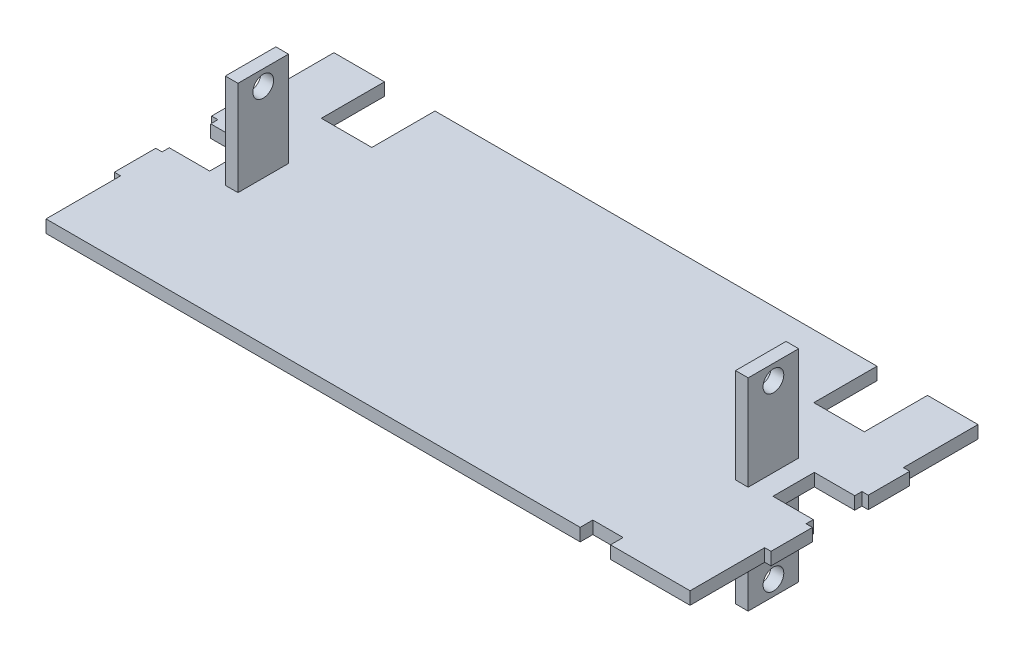
SolidWorks part; units mm, degrees
ref_plane "Front Plane" through (0, 0, 0) normal (0, 0, 1) x (1, 0, 0)
ref_plane "Top Plane" through (0, 0, 0) normal (0, 1, 0) x (1, 0, 0)
ref_plane "Right Plane" through (0, 0, 0) normal (1, 0, 0) x (0, 0, -1)
sketch "Sketch1" plane through (0, 0, 0) normal (0, 1, 0) x (1, 0, 0)
  line L0 (0, 72.39) -> (0, -72.39) construction
  line L1 (161.925, -72.39) -> (121.92, -72.39)
  line L2 (161.925, -72.39) -> (161.925, -34.8747)
  line L3 (161.925, 72.39) -> (136.525, 72.39)
  line L4 (-161.925, -72.39) -> (-161.925, -34.8747)
  line L5 (161.925, -72.39) -> (-161.925, 72.39) construction
  line L6 (161.925, 72.39) -> (-161.925, -72.39) construction
  line L7 (161.925, 10.414) -> (141.605, 10.414)
  line L9 (161.925, -10.414) -> (141.605, -10.414)
  line L10 (141.605, 10.414) -> (141.605, -10.414)
  line L11 (-136.525, 72.39) -> (-161.925, 72.39)
  line L13 (-161.925, -10.414) -> (-141.605, -10.414)
  line L14 (-141.605, 10.414) -> (-141.605, -10.414)
  line L15 (-161.925, 10.414) -> (-141.605, 10.414)
  line L17 (-127, 0) -> (127, 0) construction
  line L18 (-161.925, 14.0467) -> (-165.1, 14.0467)
  line L20 (-161.925, 34.8747) -> (-165.1, 34.8747)
  line L21 (-165.1, 14.0467) -> (-165.1, 34.8747)
  line L22 (-161.925, -34.8747) -> (-165.1, -34.8747)
  line L23 (-165.1, -14.0467) -> (-165.1, -34.8747)
  line L24 (-161.925, -14.0467) -> (-165.1, -14.0467)
  line L27 (161.925, -14.0467) -> (165.1, -14.0467)
  line L28 (165.1, -14.0467) -> (165.1, -34.8747)
  line L29 (161.925, -34.8747) -> (165.1, -34.8747)
  line L30 (161.925, 34.8747) -> (165.1, 34.8747)
  line L31 (165.1, 14.0467) -> (165.1, 34.8747)
  line L32 (161.925, 14.0467) -> (165.1, 14.0467)
  line L34 (-161.925, 34.8747) -> (-161.925, 72.39)
  line L35 (-161.925, -14.0467) -> (-161.925, -10.414)
  line L36 (161.925, 34.8747) -> (161.925, 72.39)
  line L37 (161.925, -14.0467) -> (161.925, -10.414)
  line L38 (-161.925, 10.414) -> (-161.925, 14.0467)
  line L39 (161.925, 10.414) -> (161.925, 14.0467)
  line L40 (-136.525, 72.39) -> (-136.525, 40.64)
  line L41 (-136.525, 40.64) -> (-111.125, 40.64)
  line L42 (-111.125, 72.39) -> (-111.125, 40.64)
  line L44 (111.125, 72.39) -> (111.125, 40.64)
  line L45 (111.125, 40.64) -> (136.525, 40.64)
  line L46 (136.525, 72.39) -> (136.525, 40.64)
  line L47 (111.125, 72.39) -> (-111.125, 72.39)
  line L48 (106.68, -72.39) -> (-161.925, -72.39)
  line L50 (106.68, -72.39) -> (106.68, -66.04)
  line L51 (106.68, -66.04) -> (121.92, -66.04)
  line L52 (121.92, -72.39) -> (121.92, -66.04)
  point P0 (0, 0)
  point P6 (127, 0)
  point P47 (121.92, -69.215)
  dimension "D1" = 323.85
  dimension "D2" = 144.78
  dimension "D3" = 20.828
  dimension "D5" = 3.175
  dimension "D6" = 20.828
  dimension "D4" = 20.32
  dimension "D7" = 31.75
  dimension "D8" = 25.4
  dimension "D9" = 25.4
  dimension "D10" = 31.75
  dimension "D12" = 25.4
  dimension "D11" = 25.4
  dimension "D13" = 15.24
  dimension "D14" = 6.35
  dimension "D15" = 40.005
extrude "Boss-Extrude1" add sketch "Sketch1" along normal mid plane 6.35
sketch "Sketch2" plane through (0, 0, 0) normal (0, 1, 0) x (1, 0, 0)
  line L0 (-141.605, 10.414) -> (-141.605, -10.414) construction
  line L1 (125.095, -12.7) -> (131.445, -12.7)
  line L2 (125.095, -12.7) -> (125.095, 12.7)
  line L3 (125.095, 12.7) -> (131.445, 12.7)
  line L4 (131.445, -12.7) -> (131.445, 12.7)
  line L5 (125.095, -12.7) -> (131.445, 12.7) construction
  line L6 (125.095, 12.7) -> (131.445, -12.7) construction
  line L9 (-125.095, -12.7) -> (-125.095, 12.7)
  line L10 (-125.095, 12.7) -> (-131.445, 12.7)
  line L11 (-131.445, -12.7) -> (-131.445, 12.7)
  line L12 (-125.095, -12.7) -> (-131.445, -12.7)
  line L13 (141.605, -10.414) -> (141.605, 10.414) construction
  point P0 (128.27, 0)
  point P10 (141.605, 0)
  dimension "D1" = 10.16
  dimension "D2" = 10.16
  dimension "D3" = 25.4
  dimension "D4" = 25.4
  dimension "D5" = 6.35
  dimension "D6" = 6.35
  dimension "D7" = 6.35
extrude "Boss-Extrude2" add sketch "Sketch2" along normal mid plane 101.6
sketch "Sketch3" plane through (-131.445, 0, 0) normal (-1, 0, 0) x (0, 0, 1)
  line L0 (-12.7, 50.8) -> (12.7, 50.8) construction
  line L1 (-12.7, -50.8) -> (12.7, -50.8) construction
  circle A0 centre (0, 43.18) radius 5.207
  circle A1 centre (0, -43.18) radius 5.207
  point P4 (0, 50.8)
  dimension "D1" = 10.414
  dimension "D2" = 10.414
  dimension "D3" = 7.62
  dimension "D4" = 7.62
  dimension "D5" = 86.36
extrude "Cut-Extrude1" cut sketch "Sketch3" against normal through all both and the other way through all
equation "\"length\"= 12.75"
equation "\"width\"= 5.7"
equation "\"height\"= 0.25"
equation "\"D1@Sketch1\"=\"length\""
equation "\"D2@Sketch1\"=\"width\""
equation "\"eyebolt width\"= 0.82"
equation "\"eyebolt length\"= 0.8"
equation "\"D3@Sketch1\"=\"eyebolt width\""
equation "\"D4@Sketch1\"=\"eyebolt length\""
equation "\"lead screw holder height\"= 2.76"
equation "\"lead screw diameter\"=0.41"
equation "\"D1@Sketch3\"=\"lead screw diameter\""
equation "\"distance from holders to board\"=0.4"
equation "\"D2@Sketch3\"=\"lead screw diameter\""
equation "\"lead_screw_dist\"=3.4"
equation "\"D5@Sketch3\"=\"lead_screw_dist\""
